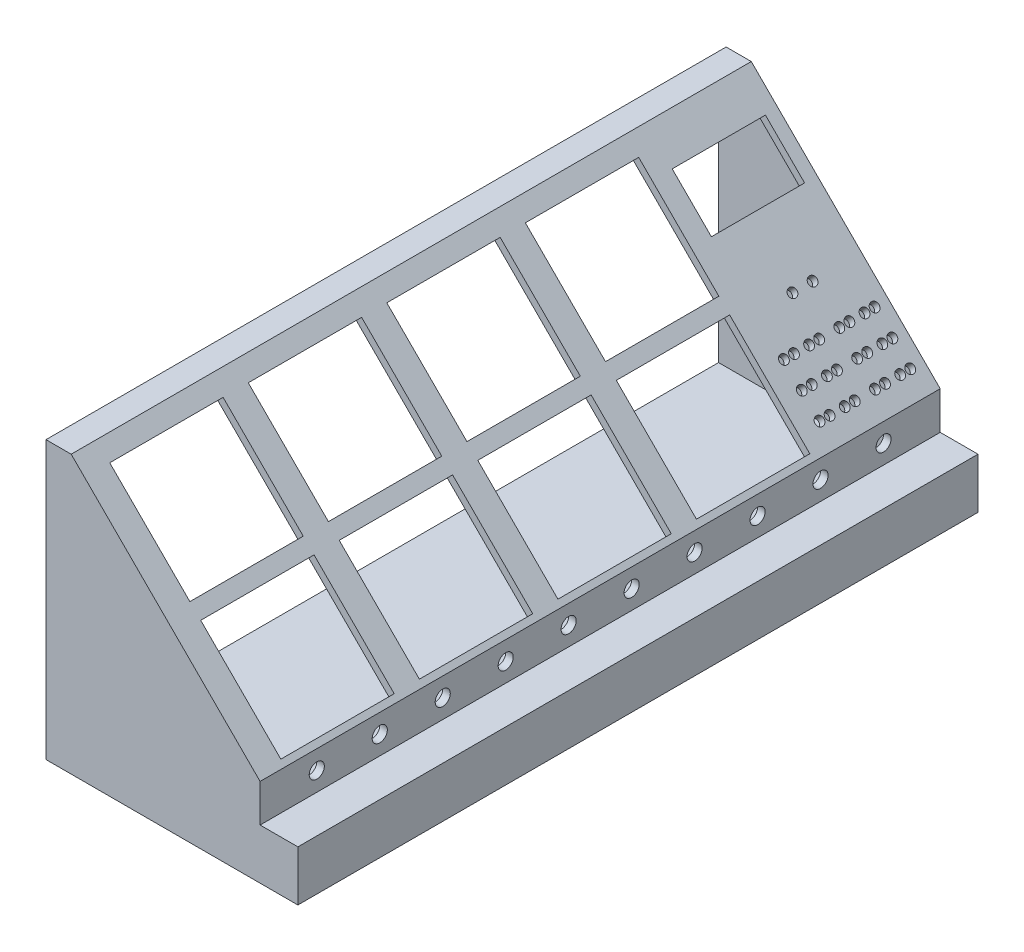
SolidWorks part; units mm, degrees
material "有机玻璃 (TM) GS 丙烯酸铸钣"
ref_plane "前视基准面" through (0, 0, 0) normal (0, 0, 1) x (1, 0, 0)
ref_plane "上视基准面" through (0, 0, 0) normal (0, 1, 0) x (1, 0, 0)
ref_plane "右视基准面" through (0, 0, 0) normal (1, 0, 0) x (0, 0, -1)
sketch "草图1" plane through (0, 0, 0) normal (0, 0, 1) x (1, 0, 0)
  line L0 (-93.61, -20) -> (6.39, -20)
  line L4 (-83.61, 90) -> (-93.61, 90)
  line L5 (-93.61, 90) -> (-93.61, -20)
  line L6 (6.39, -20) -> (6.39, 0)
  line L7 (6.39, 0) -> (-8.61, 0)
  line L8 (-8.61, 0) -> (-8.61, 15)
  line L12 (-83.61, 90) -> (-8.61, 15)
extrude "凸台-拉伸1" add sketch "草图1" along normal blind 270 contours L12 L8 L7 L6 L0 L5 L4
shell "抽壳6" thickness 3 removed face at (-93.61, 35, 135)
sketch "草图8" plane through (3.195, 3.195, 0) normal (0.7071, 0.7071, 0) x (0, 0, -1)
  line L0 (-260, 64.1948) -> (-215, 64.1948)
  line L1 (-260, 115.2608) -> (-215, 115.2608)
  line L2 (-260, 115.2608) -> (-260, 70.2608)
  line L3 (-260, 70.2608) -> (-215, 70.2608)
  line L4 (-215, 115.2608) -> (-215, 70.2608)
  line L5 (-205, 115.2608) -> (-160, 115.2608)
  line L6 (-205, 115.2608) -> (-205, 70.2608)
  line L7 (-205, 70.2608) -> (-160, 70.2608)
  line L8 (-160, 115.2608) -> (-160, 70.2608)
  line L17 (-260, 64.1948) -> (-260, 19.1948)
  line L18 (-260, 19.1948) -> (-215, 19.1948)
  line L19 (-215, 64.1948) -> (-215, 19.1948)
  line L20 (-150, 115.2608) -> (-105, 115.2608)
  line L21 (-150, 115.2608) -> (-150, 70.2608)
  line L22 (-150, 70.2608) -> (-105, 70.2608)
  line L23 (-105, 115.2608) -> (-105, 70.2608)
  line L24 (-205, 64.1948) -> (-160, 64.1948)
  line L25 (-205, 64.1948) -> (-205, 19.1948)
  line L26 (-205, 19.1948) -> (-160, 19.1948)
  line L27 (-160, 64.1948) -> (-160, 19.1948)
  line L28 (-95, 115.2608) -> (-50, 115.2608)
  line L29 (-95, 115.2608) -> (-95, 70.2608)
  line L30 (-95, 70.2608) -> (-50, 70.2608)
  line L31 (-50, 115.2608) -> (-50, 70.2608)
  line L32 (-150, 64.1948) -> (-105, 64.1948)
  line L33 (-150, 64.1948) -> (-150, 19.1948)
  line L34 (-150, 19.1948) -> (-105, 19.1948)
  line L35 (-105, 64.1948) -> (-105, 19.1948)
  line L36 (-95, 64.1948) -> (-50, 64.1948)
  line L37 (-95, 64.1948) -> (-95, 19.1948)
  line L38 (-95, 19.1948) -> (-50, 19.1948)
  line L39 (-50, 64.1948) -> (-50, 19.1948)
  line L43 (-42, 107.7608) -> (-5, 107.7608)
  line L44 (-42, 107.7608) -> (-42, 85.7608)
  line L45 (-42, 85.7608) -> (-5, 85.7608)
  line L46 (-5, 107.7608) -> (-5, 85.7608)
  circle A28 centre (-19.5, 45.7608) radius 1.75
  circle A29 centre (-15.5, 45.7608) radius 1.75
  circle A30 centre (-9.5, 45.7608) radius 1.75
  circle A31 centre (-5.5, 45.7608) radius 1.75
  circle A48 centre (-27.5, 45.7608) radius 1.75
  circle A49 centre (-31.5, 45.7608) radius 1.75
  circle A50 centre (-37.5, 45.7608) radius 1.75
  circle A51 centre (-41.5, 45.7608) radius 1.75
  circle A52 centre (-5.5, 35.7608) radius 1.75
  circle A53 centre (-9.5, 35.7608) radius 1.75
  circle A54 centre (-15.5, 35.7608) radius 1.75
  circle A55 centre (-19.5, 35.7608) radius 1.75
  circle A56 centre (-27.5, 35.7608) radius 1.75
  circle A57 centre (-31.5, 35.7608) radius 1.75
  circle A58 centre (-37.5, 35.7608) radius 1.75
  circle A59 centre (-41.5, 35.7608) radius 1.75
  circle A60 centre (-41.5, 25.7608) radius 1.75
  circle A61 centre (-37.5, 25.7608) radius 1.75
  circle A62 centre (-31.5, 25.7608) radius 1.75
  circle A63 centre (-27.5, 25.7608) radius 1.75
  circle A64 centre (-19.5, 25.7608) radius 1.75
  circle A65 centre (-15.5, 25.7608) radius 1.75
  circle A66 centre (-9.5, 25.7608) radius 1.75
  circle A67 centre (-5.5, 25.7608) radius 1.75
  circle A68 centre (-19.5, 60.7608) radius 1.75
  circle A69 centre (-27.5, 60.7608) radius 1.75
extrude "切除-拉伸1" cut sketch "草图8" against normal through all contours L2 L1 L4 L3
extrude "切除-拉伸3" cut sketch "草图8<5>" against normal blind 10
sketch "草图8<5>" plane through (3.195, 3.195, 0) normal (0.7071, 0.7071, 0) x (0, 0, -1) same geometry as "草图8"
sketch "草图10" plane through (-8.61, 0, 0) normal (1, 0, 0) x (0, 0, -1)
  circle A10 centre (-247.5, 7.5) radius 3
  circle A11 centre (-222.5, 7.5) radius 3
  circle A12 centre (-97.5, 7.5) radius 3
  circle A13 centre (-122.5, 7.5) radius 3
  circle A14 centre (-147.5, 7.5) radius 3
  circle A15 centre (-172.5, 7.5) radius 3
  circle A16 centre (-197.5, 7.5) radius 3
  circle A17 centre (-72.5, 7.5) radius 3
  circle A18 centre (-47.5, 7.5) radius 3
  circle A19 centre (-22.5, 7.5) radius 3
extrude "切除-拉伸4" cut sketch "草图10" against normal blind 3
sketch "草图15" plane through (0, -20, 0) normal (0, -1, 0) x (1, 0, 0)
  circle A0 centre (-31.11, 192.5) radius 1.5
  circle A1 centre (-13.61, 192.5) radius 1.5
  circle A2 centre (-3.61, 240) radius 1.5
  circle A3 centre (-31.11, 240) radius 1.5
extrude "切除-拉伸5" cut sketch "草图15" against normal blind 3
